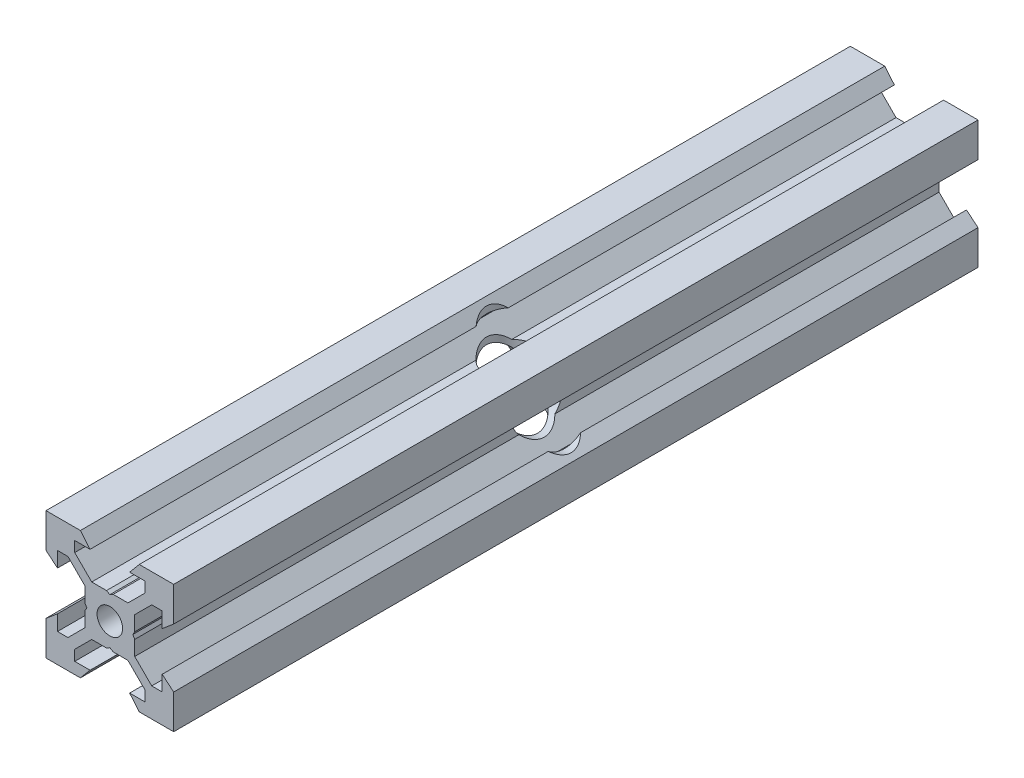
SolidWorks part; units mm, degrees
material "3.3535 (EN-AW 5754)"
ref_plane "Front Plane" through (0, 0, 0) normal (0, 0, 1) x (1, 0, 0)
ref_plane "Top Plane" through (0, 0, 0) normal (0, 1, 0) x (1, 0, 0)
ref_plane "Right Plane" through (0, 0, 0) normal (1, 0, 0) x (0, 0, -1)
sketch "Sketch1" plane through (0, 0, 0) normal (0, 0, 1) x (1, 0, 0)
  line L0 (10, 10) -> (4.6104, 10) construction
  line L1 (10, 10) -> (10, 4.6104) construction
  line L2 (10, -10) -> (10, -4.6104) construction
  line L3 (10, -10) -> (4.6104, -10) construction
  line L4 (10, 10) -> (10, 4.6104)
  line L5 (6.5607, 5.5) -> (8.2, 5.5)
  line L6 (5.5, 8.2) -> (5.5, 6.5607)
  line L7 (10, 10) -> (4.6104, 10)
  line L8 (10, 10) -> (10, 4.6104)
  line L9 (6.5607, 5.5) -> (3.9, 2.8393)
  line L10 (5.5, 6.5607) -> (2.8393, 3.9)
  line L11 (10, 4.6104) -> (8.2, 3.1)
  line L12 (4.6104, 10) -> (3.1, 8.2)
  line L13 (8.2, 3.1) -> (8.2, 5.5)
  line L14 (3.1, 8.2) -> (5.5, 8.2)
  line L15 (-6.5607, 5.5) -> (-8.2, 5.5)
  line L16 (6.5607, -5.5) -> (8.2, -5.5)
  line L17 (3.1, -8.2) -> (5.5, -8.2)
  line L18 (8.2, -3.1) -> (8.2, -5.5)
  line L19 (4.6104, -10) -> (3.1, -8.2)
  line L20 (10, -4.6104) -> (8.2, -3.1)
  line L21 (0.5196, -3.9) -> (0, -3.6)
  line L22 (0.5196, 3.9) -> (0, 3.6)
  line L23 (3.6, 0) -> (3.9, -0.5196)
  line L24 (3.9, 0.5196) -> (3.6, 0)
  line L25 (3.9, 0.5196) -> (3.9, 2.8393)
  line L26 (2.8393, 3.9) -> (0.5196, 3.9)
  line L27 (3.9, -2.8393) -> (3.9, -0.5196)
  line L28 (2.8393, -3.9) -> (0.5196, -3.9)
  line L29 (5.5, -6.5607) -> (2.8393, -3.9)
  line L30 (6.5607, -5.5) -> (3.9, -2.8393)
  line L31 (10, -10) -> (10, -4.6104)
  line L32 (10, -10) -> (4.6104, -10)
  line L33 (5.5, -8.2) -> (5.5, -6.5607)
  line L34 (-6.5607, -5.5) -> (-8.2, -5.5)
  line L35 (10, -10) -> (10, -4.6104)
  line L36 (0, 0) -> (0, 8.2) construction
  line L37 (-10, -10) -> (-4.6104, -10) construction
  line L38 (-10, -10) -> (-10, -4.6104) construction
  line L39 (-10, 10) -> (-10, 4.6104) construction
  line L40 (-10, 10) -> (-4.6104, 10) construction
  line L41 (-10, -10) -> (-10, -4.6104)
  line L43 (-5.5, -8.2) -> (-5.5, -6.5607)
  line L44 (-10, -10) -> (-4.6104, -10)
  line L45 (-10, -10) -> (-10, -4.6104)
  line L46 (-6.5607, -5.5) -> (-3.9, -2.8393)
  line L47 (-5.5, -6.5607) -> (-2.8393, -3.9)
  line L48 (-2.8393, -3.9) -> (-0.5196, -3.9)
  line L49 (-3.9, -2.8393) -> (-3.9, -0.5196)
  line L50 (-2.8393, 3.9) -> (-0.5196, 3.9)
  line L51 (-3.9, 0.5196) -> (-3.9, 2.8393)
  line L52 (-3.9, 0.5196) -> (-3.6, 0)
  line L53 (-3.6, 0) -> (-3.9, -0.5196)
  line L54 (-0.5196, 3.9) -> (0, 3.6)
  line L55 (-0.5196, -3.9) -> (0, -3.6)
  line L56 (-10, -4.6104) -> (-8.2, -3.1)
  line L57 (-4.6104, -10) -> (-3.1, -8.2)
  line L58 (-8.2, -3.1) -> (-8.2, -5.5)
  line L59 (-3.1, -8.2) -> (-5.5, -8.2)
  line L60 (-10, -10) -> (10, -10) construction
  line L61 (-10, -10) -> (-10, 10) construction
  line L62 (-3.1, 8.2) -> (-5.5, 8.2)
  line L63 (-8.2, 3.1) -> (-8.2, 5.5)
  line L64 (-4.6104, 10) -> (-3.1, 8.2)
  line L65 (-10, 4.6104) -> (-8.2, 3.1)
  line L66 (-5.5, 6.5607) -> (-2.8393, 3.9)
  line L67 (-6.5607, 5.5) -> (-3.9, 2.8393)
  line L68 (-10, 10) -> (-10, 4.6104)
  line L69 (-10, 10) -> (-4.6104, 10)
  line L70 (-5.5, 8.2) -> (-5.5, 6.5607)
  line L71 (-10, 10) -> (10, 10) construction
  line L72 (-10, 10) -> (-10, 4.6104)
  line L73 (10, -10) -> (10, 10) construction
  line L74 (-10, -10) -> (10, 10) construction
  line L75 (-10, 10) -> (10, -10) construction
  circle A0 centre (0, 0) radius 2
  dimension "D7" = 4
  dimension "D1" = 20
  dimension "D2" = 5.3896
  dimension "D3" = 4.5
  dimension "D4" = 50
  dimension "D5" = 1.8
  dimension "D6" = 1.5104
  dimension "D8" = 5.5
  dimension "D9" = 120
  dimension "D10" = 0.3
  dimension "D11" = 2.3197
  dimension "D12" = 7.8
  dimension "D13" = 7.8
  dimension "D14" = 1.5
  dimension "D15" = 2.6607
extrude "Boss-Extrude1" add sketch "Sketch1" along normal blind 126 contours L70 L62 L64 L69 L68 L65 L63 L15 L67 L51 L52 L53 L49 L46 L34 L58 L56 L41 L44 L57 L59 L43 L47 L48 L55 L21 L28 L29 L33 L17 L19 L32 L31 L20 L18 L16 L30 L27 L23 L24 L25 L9 L5 L13 L11 L4 L7 L12 L14 L6 L10 region at (9.7172, 7.3052, 0)
sketch "Sketch4" plane through (0, 0, 0) normal (1, 0, 0) x (0, 0, -1)
  line L0 (-126, 0) -> (0, 0) construction
  circle A0 centre (-63, 0) radius 4
  dimension "D1" = 8
extrude "Cut-Extrude1" cut sketch "Sketch4" against normal through all both and the other way through all
sketch "Sketch5" plane through (0, 0, 0) normal (0, 1, 0) x (1, 0, 0)
  line L0 (0, 0) -> (0, -126) construction
  circle A0 centre (0, -63) radius 4
  dimension "D1" = 8
extrude "Cut-Extrude2" cut sketch "Sketch5" against normal through all both and the other way through all
